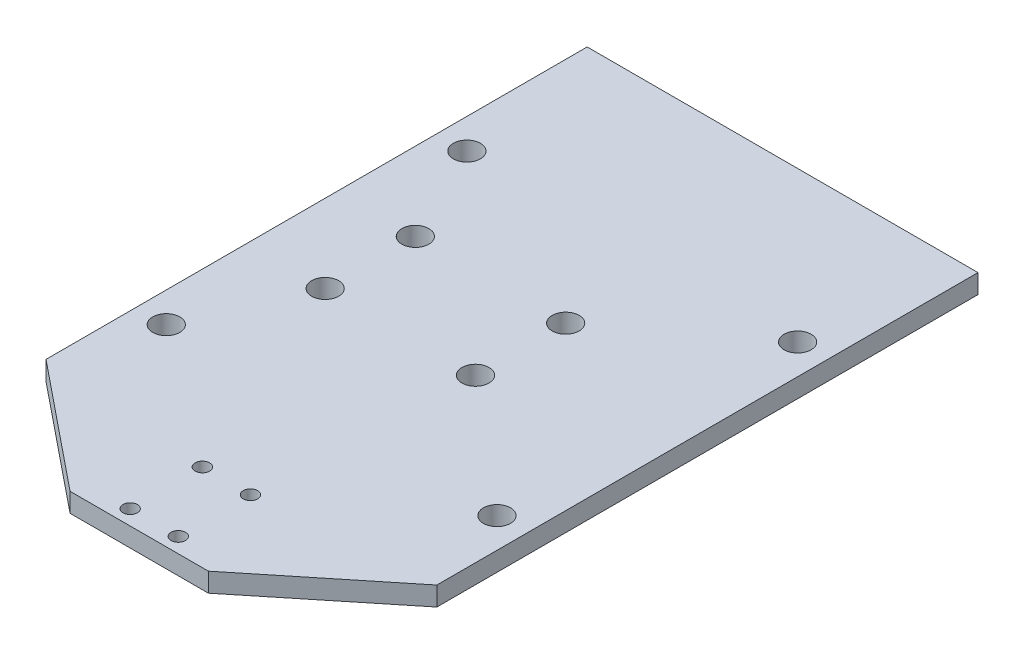
SolidWorks part; units mm, degrees
material "6061-T6 (SS)"
ref_plane "Front Plane" through (0, 0, 0) normal (0, 0, 1) x (1, 0, 0)
ref_plane "Top Plane" through (0, 0, 0) normal (0, 1, 0) x (1, 0, 0)
ref_plane "Right Plane" through (0, 0, 0) normal (1, 0, 0) x (0, 0, -1)
sketch "Sketch1" plane through (0, 0, 0) normal (0, 1, 0) x (1, 0, 0)
  line L0 (-11.5, -62) -> (-32.5, -45)
  line L1 (32.5, -45) -> (-32.5, -45)
  line L2 (32.5, -45) -> (32.5, 45)
  line L3 (32.5, 45) -> (-32.5, 45)
  line L4 (-32.5, -45) -> (-32.5, 45)
  line L5 (32.5, -45) -> (-32.5, 45) construction
  line L6 (32.5, 45) -> (-32.5, -45) construction
  line L7 (-11.5, -45) -> (11.5, -45)
  line L8 (-11.5, -45) -> (-11.5, -62)
  line L9 (-11.5, -62) -> (11.5, -62)
  line L10 (11.5, -45) -> (11.5, -62)
  line L11 (11.5, -62) -> (32.5, -45)
  line L12 (-32.5, -45) -> (32.5, -45)
  line L13 (11.5, -62) -> (-11.5, -62)
  point P0 (0, 0)
  point P10 (0, -62)
  dimension "D1" = 90
  dimension "D2" = 65
  dimension "D3" = 23
  dimension "D4" = 17
  dimension "D5" = 32.5
extrude "Boss-Extrude1" add sketch "Sketch1" along normal mid plane 3.175 contours L8 L1 L0 | L10 L11 L1 | L4 L1 L2 L3 | L10 L1 L8 L9 region at (-18.5, 0, 50.6667) region at (0, 0, 53.5) region at (0, 0, 0) region at (18.5, 0, 50.6667)
sketch "Sketch4" plane through (0, 1.5875, 0) normal (0, 1, 0) x (1, 0, 0)
  line L0 (-11.5, -62) -> (11.5, -62) construction
  point P0 (-4, -59.5)
  point P2 (4, -59.5)
  point P4 (4, -47.5)
  point P6 (-4, -47.5)
  point P16 (0, -62)
  dimension "D1" = 8
  dimension "D2" = 12
  dimension "D3" = 4
  dimension "D4" = 2.5
hole_wizard "M2 Clearance Hole1" positions "Sketch4" profile "Sketch3" hole size "M2" standard "ANSI Metric" end condition through all
sketch "Sketch3" plane through (-4, 1.5875, 59.5) normal (1, 0, 0) x (0, 0, 1)
  line L0 (0, 0) -> (0, 3.175)
  line L1 (0, 3.175) -> (1.2, 3.175)
  line L2 (1.2, 3.175) -> (1.2, 0)
  line L5 (1.2, 0) -> (0, 0)
  line L11 (0, -6.35) -> (0, 107.95) construction
  dimension "Thru Hole Dia." = 2.4
  dimension "Thru Hole Depth" = 3.175
sketch "Sketch7" plane through (0, 1.5875, 0) normal (0, 1, 0) x (1, 0, 0)
  line L0 (-32.5, -45) -> (-32.5, 45) construction
  line L1 (32.5, -45) -> (32.5, 45) construction
  line L2 (32.5, 45) -> (-32.5, 45) construction
  point P0 (-27.5, 20)
  point P2 (27.5, 20)
  point P4 (27.5, -30)
  point P6 (-27.5, -30)
  dimension "D1" = 5
  dimension "D2" = 5
  dimension "D3" = 25
  dimension "D4" = 50
hole_wizard "M4 Clearance Hole1" positions "Sketch7" profile "Sketch6" hole size "M4" standard "ANSI Metric" end condition through all
sketch "Sketch6" plane through (-27.5, 1.5875, -20) normal (1, 0, 0) x (0, 0, 1)
  line L0 (0, 0) -> (0, 3.175)
  line L1 (0, 3.175) -> (2.25, 3.175)
  line L2 (2.25, 3.175) -> (2.25, 0)
  line L5 (2.25, 0) -> (0, 0)
  line L11 (0, -6.35) -> (0, 107.95) construction
  dimension "Thru Hole Dia." = 4.5
  dimension "Thru Hole Depth" = 3.175
hole_wizard "M4 Clearance Hole2" positions "Sketch10" profile "Sketch9" hole size "M4" standard "ANSI Metric" end condition through all
sketch "Sketch10" plane through (0, 1.5875, 0) normal (0, 1, 0) x (1, 0, 0)
  point P0 (-19.5, -11.575)
  point P3 (-19.5, 3.425)
  point P6 (5.5, 3.425)
  point P9 (5.5, -11.575)
sketch "Sketch9" plane through (-19.5, 1.5875, 11.575) normal (1, 0, 0) x (0, 0, 1)
  line L0 (0, 0) -> (0, 3.175)
  line L1 (0, 3.175) -> (2.25, 3.175)
  line L2 (2.25, 3.175) -> (2.25, 0)
  line L5 (2.25, 0) -> (0, 0)
  line L11 (0, -6.35) -> (0, 107.95) construction
  dimension "Thru Hole Dia." = 4.5
  dimension "Thru Hole Depth" = 3.175
